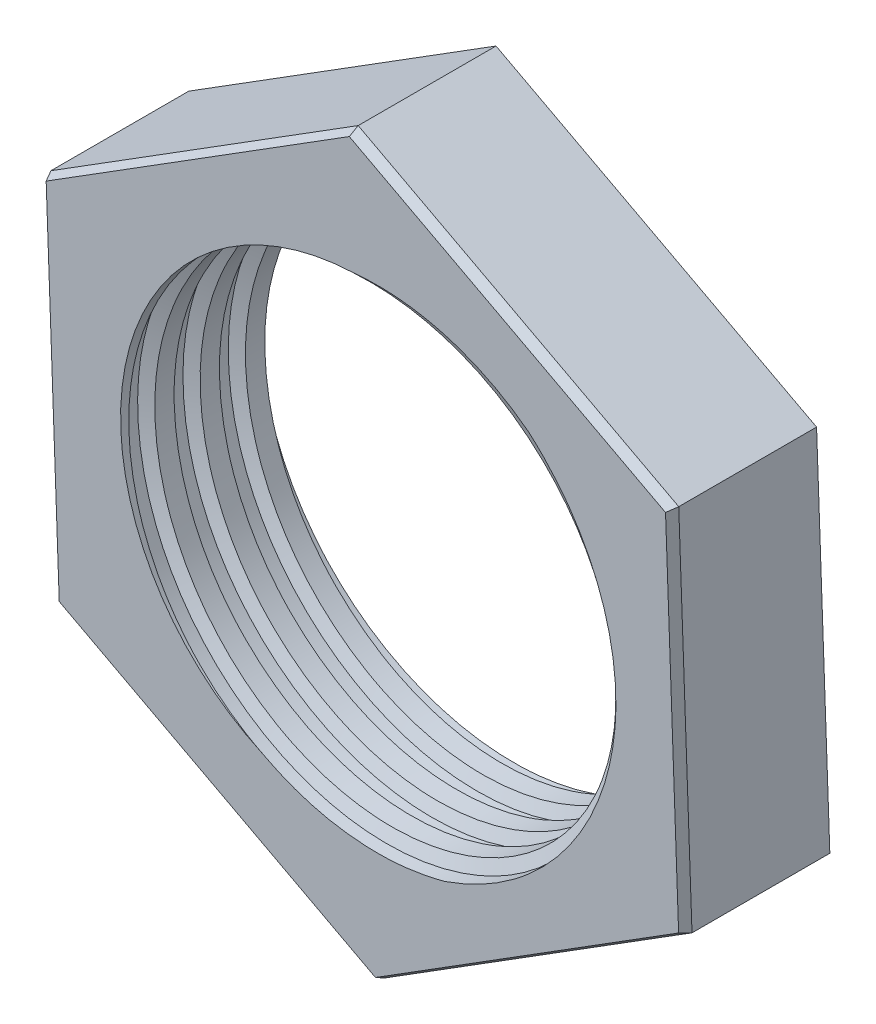
SolidWorks part; units mm, degrees
ref_plane "Front Plane" through (0, 0, 0) normal (0, 0, 1) x (1, 0, 0)
ref_plane "Top Plane" through (0, 0, 0) normal (0, 1, 0) x (1, 0, 0)
ref_plane "Right Plane" through (0, 0, 0) normal (1, 0, 0) x (0, 0, -1)
sketch "Sketch1" plane through (0, 0, 0) normal (0, 0, 1) x (1, 0, 0)
  line L1 (10.1658, 6.3762) -> (-0.439, 11.992)
  line L2 (-0.439, 11.992) -> (-10.6049, 5.6158)
  line L3 (-10.6049, 5.6158) -> (-10.1658, -6.3762)
  line L4 (-10.1658, -6.3762) -> (0.439, -11.992)
  line L5 (0.439, -11.992) -> (10.6049, -5.6158)
  line L6 (10.6049, -5.6158) -> (10.1658, 6.3762)
  circle A0 centre (0, 0) radius 8
  circle A1 centre (0, 0) radius 10.3923 construction
  dimension "D1" = 16
  dimension "D2" = 12
extrude "Boss-Extrude1" add sketch "Sketch1" along normal blind 5
sketch "Sketch2" plane through (0, 0, 5) normal (0, 0, 1) x (1, 0, 0)
  circle A0 centre (0, 0) radius 8
curve "Helix/Spiral1" pitch 1.5 height 5 turns 3.3333
sketch "Sketch3" plane through (0, 0, 0) normal (0, 1, 0) x (1, 0, 0)
  line L0 (-7.8511, -2.7961) -> (-8.3872, -2.7961) construction
  line L1 (-7.8511, -2.2961) -> (-7.8511, -3.2961)
  line L2 (-7.8511, -3.2961) -> (-8.3872, -3.0461)
  line L3 (-8.3872, -3.0461) -> (-8.3872, -2.5461)
  line L4 (-7.8511, -2.2961) -> (-8.3872, -2.5461)
  spline S0 degree 3 poles (8, -5) (8, -4.9688) (7.5781, -4.9056) (5.7773, -4.8113) (3.0859, -4.717) (-0.0811, -4.6226) (-3.2356, -4.5283) (-5.8914, -4.434) (-7.6391, -4.3396) (-8.2093, -4.2453) (-7.5142, -4.1509) (-5.6609, -4.0566) (-2.935, -3.9623) (0.2433, -3.8679) (3.3841, -3.7736) (6.0033, -3.6792) (7.6971, -3.5849) (8.2045, -3.4906) (7.4473, -3.3962) (5.5422, -3.3019) (2.7829, -3.2075) (-0.4054, -3.1132) (-3.5312, -3.0189) (-6.1128, -2.9245) (-7.7521, -2.8302) (-8.1965, -2.7358) (-7.3776, -2.6415) (-5.4215, -2.5472) (-2.6297, -2.4528) (0.5674, -2.3585) (3.677, -2.2642) (6.2199, -2.1698) (7.804, -2.0755) (8.1853, -1.9811) (7.3049, -1.8868) (5.2986, -1.7925) (2.4755, -1.6981) (-0.7291, -1.6038) (-3.8213, -1.5094) (-6.3246, -1.4151) (-7.8529, -1.3208) (-8.1709, -1.2264) (-7.2294, -1.1321) (-5.1736, -1.0377) (-2.3204, -0.9434) (0.8905, -0.8491) (3.9642, -0.7547) (6.4268, -0.6604) (7.8988, -0.566) (8.1533, -0.4717) (7.151, -0.3774) (5.0468, -0.283) (2.1636, -0.1887) (-1.0489, -0.0944) (-3.0933, -0.0312) (-4, 0) knots 0 0 0 0 0.018868 0.037736 0.056604 0.075472 0.09434 0.113208 0.132075 0.150943 0.169811 0.188679 0.207547 0.226415 0.245283 0.264151 0.283019 0.301887 0.320755 0.339623 0.358491 0.377358 0.396226 0.415094 0.433962 0.45283 0.471698 0.490566 0.509434 0.528302 0.54717 0.566038 0.584906 0.603774 0.622642 0.641509 0.660377 0.679245 0.698113 0.716981 0.735849 0.754717 0.773585 0.792453 0.811321 0.830189 0.849057 0.867925 0.886792 0.90566 0.924528 0.943396 0.962264 0.981132 1 1 1 1 construction
  dimension "D1" = 0.5
  dimension "D2" = 0.25
  dimension "D3" = 65
sweep "Cut-Sweep1" cut profiles "Sketch3" path "Helix/Spiral1"
chamfer "Chamfer1" distance 0.3 angle 25 12 edges at (5.5219, -8.8039, 5) (-4.8634, -9.1841, 5) (-10.3853, -0.3802, 5) (-5.5219, 8.8039, 5) (4.8634, 9.1841, 5) (10.3853, 0.3802, 5) (-10.3853, -0.3802, 0) (-4.8634, -9.1841, 0) (5.5219, -8.8039, 0) (10.3853, 0.3802, 0) (4.8634, 9.1841, 0) (-5.5219, 8.8039, 0)
